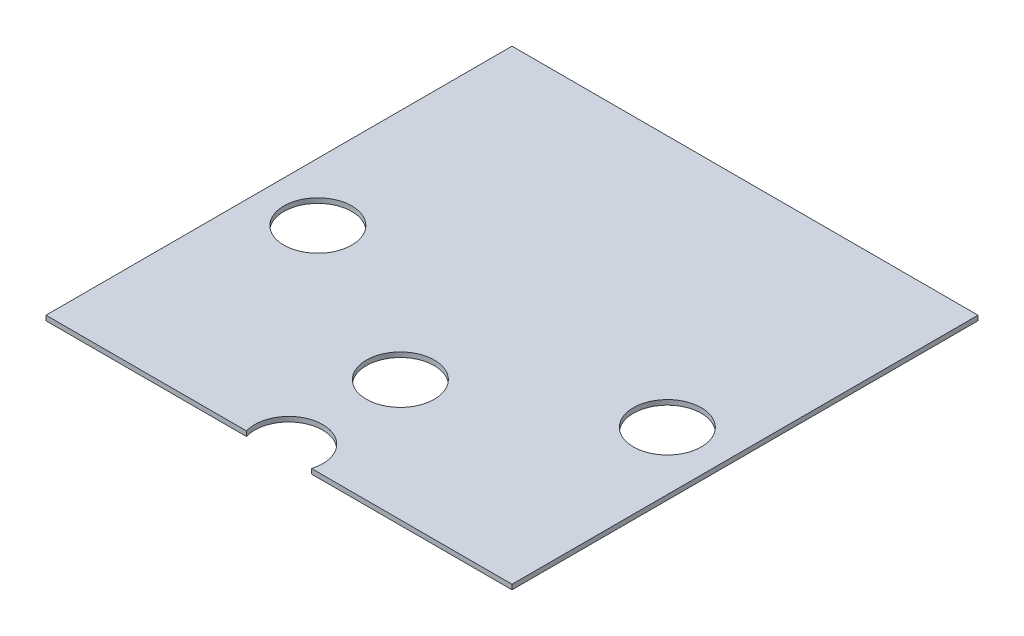
SolidWorks part; units mm, degrees
ref_plane "Front Plane" through (0, 0, 0) normal (0, 0, 1) x (1, 0, 0)
ref_plane "Top Plane" through (0, 0, 0) normal (0, 1, 0) x (1, 0, 0)
ref_plane "Right Plane" through (0, 0, 0) normal (1, 0, 0) x (0, 0, -1)
sketch "Sketch1" plane through (0, 0, 0) normal (0, 1, 0) x (1, 0, 0)
  line L1 (-387.1576, 281.7091) -> (222.4424, 281.7091)
  line L2 (-387.1576, 281.7091) -> (-387.1576, -327.8909)
  line L3 (-387.1576, -327.8909) -> (222.4424, -327.8909)
  line L4 (222.4424, 281.7091) -> (222.4424, -327.8909)
  dimension "D1" = 609.6
  dimension "D2" = 609.6
extrude "Boss-Extrude1" add sketch "Sketch1" along normal blind 6.35
sketch "Sketch2" plane through (0, 6.35, 0) normal (0, 1, 0) x (1, 0, 0)
  line L12 (82.7424, -547.9486) -> (82.7424, -311.0332)
  line L14 (89.0924, -549.9737) -> (89.0924, -309.0081)
  line L18 (-355.4076, -429.4909) -> (-361.7576, -429.4909)
  line L19 (197.0424, -429.4909) -> (190.6924, -429.4909)
  circle A5 centre (-82.3576, -296.1409) radius 63.5
  circle A9 centre (-82.3576, -296.1409) radius 69.85
  circle A13 centre (-82.3576, -448.5409) radius 82.55
  circle A17 centre (146.2424, -48.4909) radius 50.8
  circle A21 centre (-82.3576, -588.2409) radius 44.45
  circle A25 centre (-82.3576, -150.0909) radius 63.5
  circle A29 centre (-82.3576, -169.1409) radius 44.45
  circle A33 centre (-82.3576, -315.1909) radius 44.45
  circle A37 centre (-82.3576, -480.2909) radius 44.45
  circle A143 centre (-82.3576, -150.0909) radius 69.85
  circle A145 centre (-82.3576, -448.5409) radius 76.2
  circle A147 centre (-82.3576, -721.5909) radius 44.45
  circle A149 centre (-310.9576, -48.4909) radius 44.45
  circle A151 centre (146.2424, -48.4909) radius 44.45
  circle A153 centre (-310.9576, -48.4909) radius 50.8
  arc A155 (82.7424, -311.0332) -> (82.7424, -547.9486) centre (-82.3576, -429.4909) ccw
  arc A157 (89.0924, -309.0081) -> (89.0924, -549.9737) centre (-82.3576, -429.4909) ccw
  ellipse E2 centre (-82.3576, -429.4909) end of major axis (-82.3576, -226.2909) minor radius 177.8
  ellipse E4 centre (-82.3576, -429.4909) end of major axis (-82.3576, -92.9409) minor radius 273.05 (-355.4076, -429.4909) -> (190.6924, -429.4909) ccw
  spline S2 degree 3 poles (-361.7576, -429.4909) (-361.7576, -440.6643) (-360.866, -463.0413) (-355.5354, -507.3399) (-342.2995, -561.1377) (-316.4719, -620.7036) (-281.6498, -673.014) (-239.1144, -716.0513) (-190.4497, -748.1229) (-137.5067, -767.9257) (-82.3576, -774.6235) (-27.2084, -767.9257) (25.7346, -748.1229) (74.3993, -716.0513) (116.9346, -673.014) (151.7568, -620.7036) (177.5843, -561.1377) (190.8203, -507.3399) (196.1509, -463.0413) (197.0424, -440.6643) (197.0424, -429.4909) knots 1.570796 1.570796 1.570796 1.570796 1.668971 1.767146 1.963495 2.159845 2.356194 2.552544 2.748894 2.945243 3.141593 3.337942 3.534292 3.730641 3.926991 4.12334 4.31969 4.516039 4.614214 4.712389 4.712389 4.712389 4.712389
extrude "Cut-Extrude1" cut sketch "Sketch2" against normal blind 101.6 contours A29 | A33 | A149 | A151
